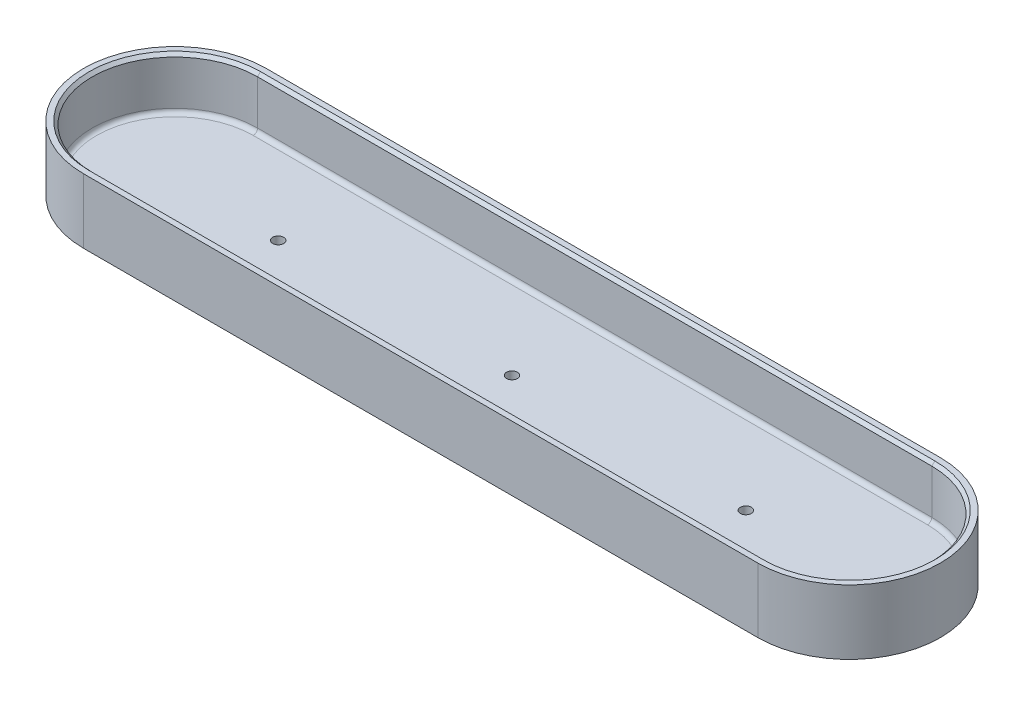
SolidWorks part; units mm, degrees
material "PLA"
ref_plane "Front Plane" through (0, 0, 0) normal (0, 0, 1) x (1, 0, 0)
ref_plane "Top Plane" through (0, 0, 0) normal (0, 1, 0) x (1, 0, 0)
ref_plane "Right Plane" through (0, 0, 0) normal (1, 0, 0) x (0, 0, -1)
sketch "Sketch1" plane through (0, 0, 0) normal (0, 1, 0) x (1, 0, 0)
  line L0 (-99.441, 0) -> (99.441, 0) construction
  line L1 (0, -55.9739) -> (0, 55.9739) construction
  line L2 (-99.441, 24.384) -> (99.441, 24.384)
  line L3 (-99.441, -24.384) -> (99.441, -24.384)
  arc A0 (-99.441, 24.384) -> (-99.441, -24.384) centre (-99.441, 0) ccw
  arc A1 (99.441, 24.384) -> (99.441, -24.384) centre (99.441, 0) cw
  circle A2 centre (-99.441, 0) radius 24.13 construction
  point P4 (0, 0)
  point P10 (0, 0)
  dimension "D2" = 0.254
  dimension "D3" = 48.26
  dimension "D1" = 198.882
extrude "MainBlock" add sketch "Sketch1" along normal blind 3.81
sketch "Sketch2" plane through (0, 0, 0) normal (0, -1, 0) x (1, 0, 0)
  line L0 (0, 0) -> (0, 50000) construction
  line L1 (-99.441, 26.924) -> (99.441, 26.924)
  line L2 (-99.441, -24.384) -> (99.441, -24.384)
  line L3 (99.441, 24.384) -> (-99.441, 24.384)
  line L5 (99.441, 24.384) -> (-99.441, 24.384)
  line L6 (-95.25, 0) -> (49904.75, 0) construction
  line L7 (99.441, -24.384) -> (-99.441, -24.384)
  line L8 (-99.441, -26.924) -> (99.441, -26.924)
  arc A0 (-99.441, 26.924) -> (-99.441, -26.924) centre (-99.441, 0) ccw
  arc A1 (99.441, 24.384) -> (99.441, -24.384) centre (99.441, 0) cw
  arc A2 (-99.441, 24.384) -> (-99.441, -24.384) centre (-99.441, 0) ccw
  arc A3 (99.441, -24.384) -> (99.441, 24.384) centre (99.441, 0) ccw
  arc A4 (-99.441, 24.384) -> (-99.441, -24.384) centre (-99.441, 0) ccw
  arc A6 (99.441, 26.924) -> (99.441, -26.924) centre (99.441, 0) cw
  point P0 (0, 24.384)
  point P15 (0, 26.924)
  point P16 (0, -24.384)
  point P19 (0, -26.924)
  dimension "D2" = 2.54
  dimension "D1" = 0
extrude "Boss-Extrude1" add sketch "Sketch2" against normal blind 19.05
sketch "Sketch3" plane through (0, 0, 0) normal (0, -1, 0) x (1, 0, 0)
  line L0 (0, 0) -> (50000, 0) construction
  line L1 (0, 0) -> (0, 50000) construction
  circle A1 centre (0, 0) radius 1.6129
  circle A8 centre (-68.961, 0) radius 1.6129
  circle A9 centre (68.961, 0) radius 1.6129
  arc A10 (99.441, -26.924) -> (99.441, 26.924) centre (99.441, 0) ccw construction
  arc A11 (-99.441, 26.924) -> (-99.441, -26.924) centre (-99.441, 0) ccw construction
  arc A12 (99.441, -26.924) -> (99.441, 26.924) centre (99.441, 0) ccw construction
  arc A13 (-99.441, 26.924) -> (-99.441, -26.924) centre (-99.441, 0) ccw construction
  dimension "0.085" = 3.2258
  dimension "D2" = 3.2258
  dimension "D3" = 3.2258
  dimension "D4" = 30.48
  dimension "D5" = 30.48
extrude "Cut-Extrude1" cut sketch "Sketch3" against normal through all
fillet "Fillet1" radius 1.27 4 edges at (123.825, 3.81, 0) (0, 3.81, 24.384) (-123.825, 3.81, 0) (0, 3.81, -24.384)
chamfer "Chamfer1" distance 0.889 angle 45 4 edges at (0, 19.05, 24.384) (-123.825, 19.05, 0) (123.825, 19.05, 0) (0, 19.05, -24.384)
equation "\"D2@Sketch3\"=\"0.085@Sketch3\""
equation "\"D3@Sketch3\"=\"0.085@Sketch3\""
